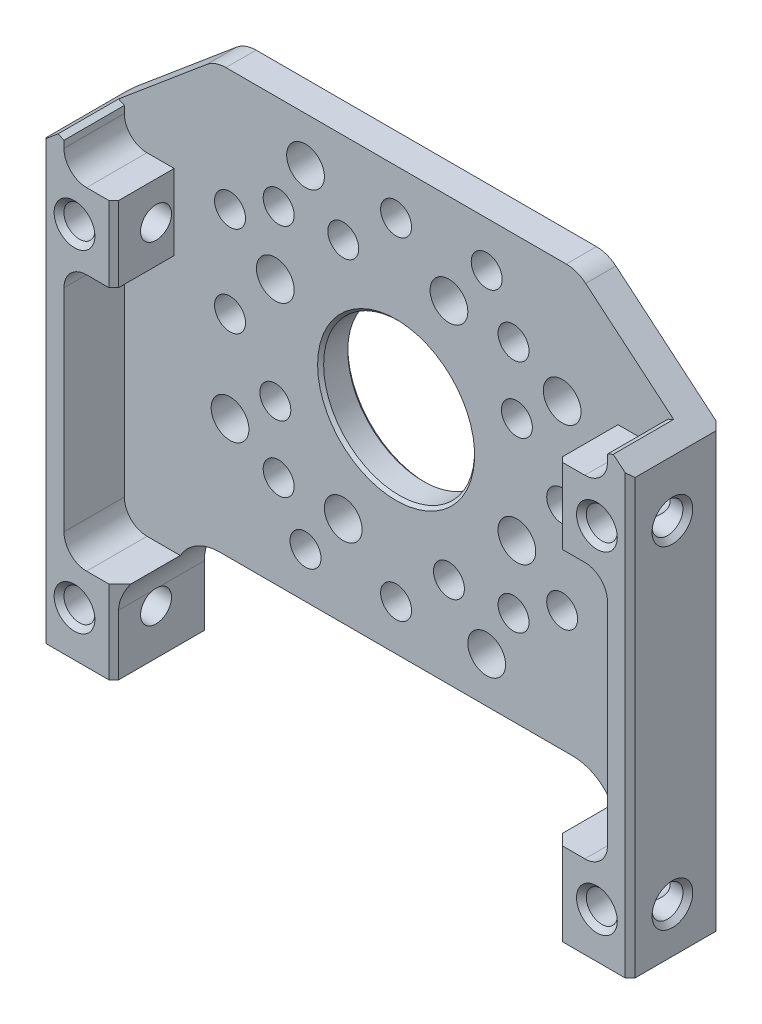
SolidWorks part; units mm, degrees
ref_plane "Front Plane" through (0, 0, 0) normal (0, 0, 1) x (1, 0, 0)
ref_plane "Top Plane" through (0, 0, 0) normal (0, 1, 0) x (1, 0, 0)
ref_plane "Right Plane" through (0, 0, 0) normal (1, 0, 0) x (0, 0, -1)
ref_plane "Plane1" through (0, 0, -17) normal (0, 0, 1) x (1, 0, 0)
sketch "Sketch1" plane through (0, 0, -17) normal (0, 0, 1) x (1, 0, 0)
  line L0 (18, 7.7068) -> (19.5, 7.7068)
  line L1 (19.5, 7.7068) -> (18, 8.9654)
  line L2 (18, 8.9654) -> (18, 7.7068)
extrude "Boss-Extrude1" add sketch "Sketch1" against normal blind 4
ref_plane "Plane2" through (0, 0, -21) normal (0, 0, 1) x (1, 0, 0)
sketch "Sketch2" plane through (0, 0, -21) normal (0, 0, 1) x (1, 0, 0)
  line L0 (-19.5, 7.7068) -> (19.5, 7.7068)
  line L1 (19.5, 7.7068) -> (12, 14)
  line L2 (12, 14) -> (-12, 14)
  line L3 (-12, 14) -> (-19.5, 7.7068)
extrude "Boss-Extrude2" add sketch "Sketch2" against normal blind 2
sketch "Sketch3" plane through (0, 7.7068, 0) normal (0, -1, 0) x (1, 0, 0)
  line L0 (-19.5, -21) -> (-14.7, -21)
  line L1 (18, -21) -> (18, -17)
  line L2 (18, -17) -> (19.5, -17)
  line L3 (19.5, -17) -> (19.5, -23)
  line L4 (19.5, -23) -> (18, -23)
  line L5 (-14.7, -23) -> (-19.5, -23)
  line L6 (-19.5, -23) -> (-19.5, -21)
  spline S0 degree 3 poles (18, -21) (7.1, -21) (-3.8, -21) (-14.7, -21) knots 0 0 0 0 1 1 1 1
  spline S1 degree 3 poles (18, -23) (7.1, -23) (-3.8, -23) (-14.7, -23) knots 0 0 0 0 1 1 1 1
extrude "Boss-Extrude3" add sketch "Sketch3" along normal blind 23.2068
sketch "Sketch4" plane through (0, -15.5, 0) normal (0, -1, 0) x (1, 0, 0)
  line L0 (18, -17) -> (18, -21)
  line L1 (18, -21) -> (18, -23)
  line L2 (18, -23) -> (19.5, -23)
  line L3 (19.5, -23) -> (19.5, -17)
  line L4 (19.5, -17) -> (18, -17)
extrude "Cut-Extrude1" cut sketch "Sketch4" against normal blind 1.5
sketch "Sketch5" plane through (18, 0, 0) normal (1, 0, 0) x (0, 0, -1)
  line L0 (21, -15.5) -> (23, -15.5)
  line L1 (23, -15.5) -> (23, -14)
  line L2 (23, -14) -> (21, -14)
  line L3 (21, -14) -> (21, -15.5)
extrude "Cut-Extrude2" cut sketch "Sketch5" against normal blind 32.7
sketch "Sketch6" plane through (0, -14, 0) normal (0, -1, 0) x (1, 0, 0)
  line L0 (14.7, -21) -> (18, -21)
  line L1 (18, -21) -> (18, -17)
  line L2 (18, -17) -> (19.5, -17)
  line L3 (19.5, -17) -> (19.5, -23)
  line L4 (19.5, -23) -> (14.7, -23)
  line L5 (14.7, -23) -> (14.7, -21)
extrude "Boss-Extrude4" add sketch "Sketch6" along normal blind 1.5
sketch "Sketch7" plane through (0, -15.5, 0) normal (0, -1, 0) x (1, 0, 0)
  line L0 (19.5, -23) -> (14.7, -23)
  line L1 (14.7, -23) -> (14.7, -17)
  line L2 (14.7, -17) -> (19.5, -17)
  line L3 (19.5, -17) -> (19.5, -23)
extrude "Boss-Extrude5" add sketch "Sketch7" along normal blind 5.5
sketch "Sketch8" plane through (0, 0, -21) normal (0, 0, 1) x (1, 0, 0)
  line L0 (-18, -15.5) -> (-19.5, -15.5)
  line L1 (-19.5, -15.5) -> (-19.5, 7.7068)
  line L2 (-19.5, 7.7068) -> (-18, 8.9654)
  line L3 (-18, 8.9654) -> (-18, -15.5)
extrude "Boss-Extrude6" add sketch "Sketch8" along normal blind 4
sketch "Sketch9" plane through (0, -15.5, 0) normal (0, -1, 0) x (1, 0, 0)
  line L0 (-19.5, -17) -> (-14.7, -17)
  line L1 (-14.7, -17) -> (-14.7, -23)
  line L2 (-14.7, -23) -> (-19.5, -23)
  line L3 (-19.5, -23) -> (-19.5, -17)
extrude "Boss-Extrude7" add sketch "Sketch9" along normal blind 5.5
sketch "Sketch10" plane through (0, 0, -21) normal (0, 0, 1) x (1, 0, 0)
  line L0 (14.7, 1.5) -> (14.7, 6.5)
  line L1 (14.7, 6.5) -> (18, 6.5)
  line L2 (18, 6.5) -> (18, 1.5)
  line L3 (18, 1.5) -> (14.7, 1.5)
extrude "Boss-Extrude8" add sketch "Sketch10" along normal blind 4
sketch "Sketch11" plane through (0, 0, -21) normal (0, 0, 1) x (1, 0, 0)
  line L0 (-14.7, 6.5) -> (-14.7, 1.5)
  line L1 (-14.7, 1.5) -> (-18, 1.5)
  line L2 (-18, 1.5) -> (-18, 6.5)
  line L3 (-18, 6.5) -> (-14.7, 6.5)
extrude "Boss-Extrude9" add sketch "Sketch11" along normal blind 4
hole_wizard "Ø2.05 (2.05) Diameter Hole1" positions "Sketch13" profile "Sketch12" hole size "Ø2.05" standard "ANSI Metric"
sketch "Sketch13" plane through (-14.7, 0, 0) normal (1, 0, 0) x (0, 0, -1)
  point P0 (19.8, 4)
  point P1 (19.8, -18)
sketch "Sketch12" plane through (-14.7, 4, -19.8) normal (0, 1, 0) x (0, 0, -1)
  line L0 (0, 0) -> (0, 4.8)
  line L1 (0, 4.8) -> (1.025, 4.8)
  line L2 (1.025, 4.8) -> (1.025, 0)
  line L5 (1.025, 0) -> (0, 0)
  line L11 (0, -6.35) -> (0, 107.95) construction
  dimension "Thru Hole Dia." = 2.05
  dimension "Thru Hole Depth" = 4.8
hole_wizard "Ø2.05 (2.05) Diameter Hole2" positions "Sketch15" profile "Sketch14" hole size "Ø2.05" standard "ANSI Metric"
sketch "Sketch15" plane through (14.7, 0, 0) normal (-1, 0, 0) x (0, 0, 1)
  point P0 (-19.8, 4)
  point P1 (-19.8, -18)
sketch "Sketch14" plane through (14.7, 4, -19.8) normal (0, 1, 0) x (0, 0, 1)
  line L0 (0, 0) -> (0, 4.8)
  line L1 (0, 4.8) -> (1.025, 4.8)
  line L2 (1.025, 4.8) -> (1.025, 0)
  line L5 (1.025, 0) -> (0, 0)
  line L11 (0, -6.35) -> (0, 107.95) construction
  dimension "Thru Hole Dia." = 2.05
  dimension "Thru Hole Depth" = 4.8
hole_wizard "Ø2.5 (2.5) Diameter Hole1" positions "Sketch17" profile "Sketch16" hole size "Ø2.5" standard "ANSI Metric"
sketch "Sketch17" plane through (0, 0, -21) normal (0, 0, 1) x (1, 0, 0)
  point P0 (3.5, 8)
  point P1 (-8, 3.5)
  point P2 (-3.5, -8)
  point P3 (8, -3.5)
  point P4 (-6, 11)
  point P5 (-11, -6)
  point P6 (6, -11)
  point P7 (11, 6)
sketch "Sketch16" plane through (3.5, 8, -21) normal (1, 0, 0) x (0, -1, 0)
  line L0 (0, 0) -> (0, 2)
  line L1 (0, 2) -> (1.25, 2)
  line L2 (1.25, 2) -> (1.25, 0)
  line L5 (1.25, 0) -> (0, 0)
  line L11 (0, -6.35) -> (0, 107.95) construction
  dimension "Thru Hole Dia." = 2.5
  dimension "Thru Hole Depth" = 2
hole_wizard "Ø2.05 (2.05) Diameter Hole3" positions "Sketch19" profile "Sketch18" hole size "Ø2.05" standard "ANSI Metric"
sketch "Sketch19" plane through (0, 0, -23) normal (0, 0, -1) x (-1, 0, 0)
  point P0 (0, 11)
  point P1 (-7.7782, 7.7782)
  point P2 (-11, 0)
  point P3 (-7.7782, -7.7782)
  point P4 (0, -11)
  point P5 (7.7782, -7.7782)
  point P6 (11, 0)
  point P7 (7.7782, 7.7782)
  point P8 (3.5, 8)
  point P9 (8, -3.5)
  point P10 (-3.5, -8)
  point P11 (-8, 3.5)
  point P12 (11, 6)
  point P13 (6, -11)
  point P14 (-11, -6)
  point P15 (-6, 11)
sketch "Sketch18" plane through (0, 11, -23) normal (1, 0, 0) x (0, 1, 0)
  line L0 (0, 0) -> (0, 6)
  line L1 (0, 6) -> (1.025, 6)
  line L2 (1.025, 6) -> (1.025, 0)
  line L5 (1.025, 0) -> (0, 0)
  line L11 (0, -6.35) -> (0, 107.95) construction
  dimension "Thru Hole Dia." = 2.05
  dimension "Thru Hole Depth" = 6
hole_wizard "Ø10.0 (10) Diameter Hole1" positions "Sketch21" profile "Sketch20" hole size "Ø10.0" standard "ANSI Metric"
sketch "Sketch21" plane through (0, 0, -23) normal (0, 0, -1) x (-1, 0, 0)
  point P0 (0, 0)
sketch "Sketch20" plane through (0, 0, -23) normal (1, 0, 0) x (0, 1, 0)
  line L0 (0, 0) -> (0, 6)
  line L1 (0, 6) -> (5, 6)
  line L2 (5, 6) -> (5, 0)
  line L5 (5, 0) -> (0, 0)
  line L11 (0, -6.35) -> (0, 107.95) construction
  dimension "Thru Hole Dia." = 10
  dimension "Thru Hole Depth" = 6
hole_wizard "Ø2.05 (2.05) Diameter Hole4" positions "Sketch23" profile "Sketch22" hole size "Ø2.05" standard "ANSI Metric"
sketch "Sketch23" plane through (0, 0, -17) normal (0, 0, 1) x (1, 0, 0)
  point P0 (17.3, 4)
  point P1 (-17.3, 4)
  point P2 (17.3, -18)
  point P3 (-17.3, -18)
sketch "Sketch22" plane through (17.3, 4, -17) normal (1, 0, 0) x (0, -1, 0)
  line L0 (0, 0) -> (0, 9.2)
  line L1 (0, 9.2) -> (1.025, 9.2)
  line L2 (1.025, 9.2) -> (1.025, 0)
  line L5 (1.025, 0) -> (0, 0)
  line L10 (0, 9.2) -> (-1.025, 9.2) construction
  line L11 (0, -6.35) -> (0, 107.95) construction
  dimension "Hole Dia." = 2.05
  dimension "Hole Depth" = 9.2
  dimension "Drill Angle" = 180
chamfer "Chamfer1" distance 0.325 angle 45 32 edges at (-8.8032, -7.7782, -23) (-7.025, -11, -23) (-9.025, -3.5, -23) (-19.5, -18, -20.825) (19.5, 4, -18.775) (-8.8032, 7.7782, -23) (6.975, 3.5, -23) (14.7, -18.25, -17) (4.975, 11, -23) (-14.7, -18.25, -17) (-19.5, 4, -20.825) (-12.025, 0, -23) (19.5, -6.6466, -23) (-4.525, 8, -23) (-19.5, -6.6466, -23) (2.475, -8, -23) (-12.025, 6, -23) (-1.025, 11, -23) (9.975, -6, -23) (-16.275, 4, -17) (-19.5, -6.6466, -17) (-16.275, -18, -17) (19.5, -18, -18.775) (6.7532, -7.7782, -23) (-1.025, -11, -23) (19.5, -6.6466, -17) (-14.7, 4, -17) (18.325, -18, -17) (18.325, 4, -17) (6.7532, 7.7782, -23) (14.7, 4, -17) (9.975, 0, -23)
chamfer "Chamfer2" distance 0.1999 angle 45 2 edges at (-5, 0, -21) (-5, 0, -23) first distance on face at (-5, 0, -23) first distance on face at (-9.1282, -7.7782, -23)
chamfer "Chamfer3" distance 0.5 angle 65 2 edges at (18, 8.9654, -19) (-18, 8.9654, -19) first distance on face at (17.1688, 9.6629, -20.25) first distance on face at (-17.1688, 9.6629, -20.25)
fillet "Fillet1" radius 1.5 6 edges at (-18, 6.5, -19) (-18, -15.5, -19) (-18, 1.5, -19) (18, -15.5, -19) (18, 6.5, -19) (18, 1.5, -19) tangent propagation no
fillet "Fillet2" radius 2 2 edges at (-12, 14, -22) (12, 14, -22) tangent propagation no
fillet "Fillet3" radius 3 2 edges at (-14.7, -14, -22) (14.7, -14, -22) tangent propagation no
